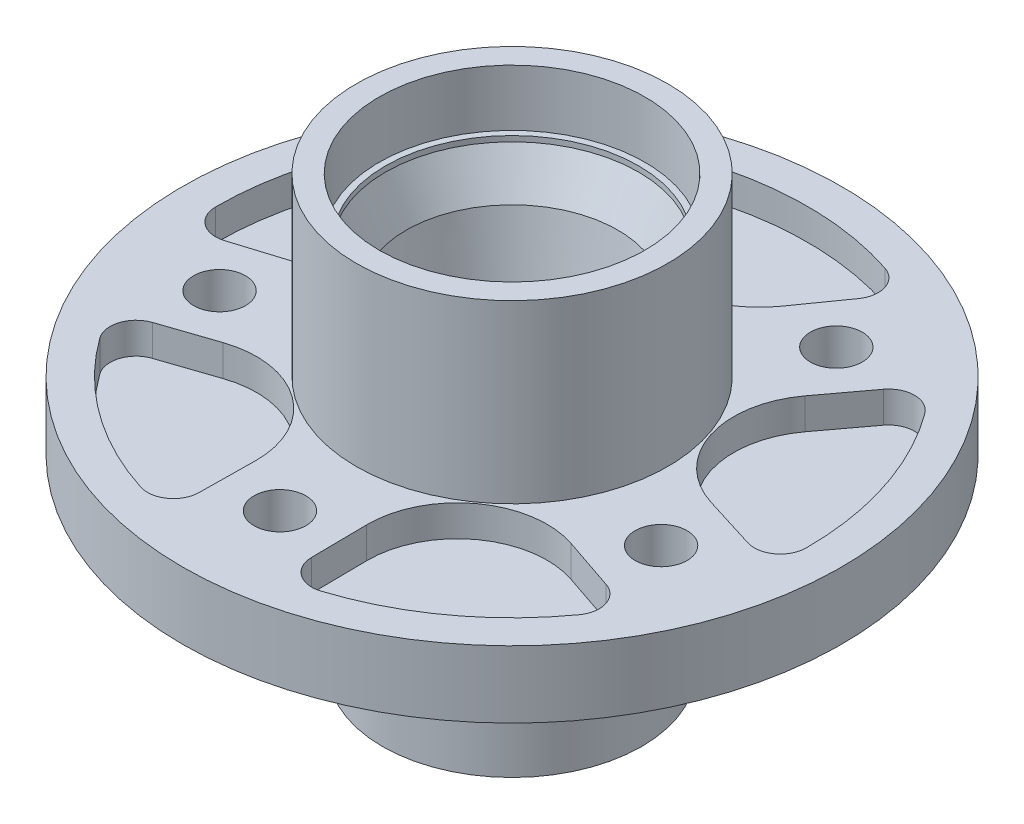
SolidWorks part; units mm, degrees
material "ASTM A36 Steel"
ref_plane "Front Plane" through (0, 0, 0) normal (0, 0, 1) x (1, 0, 0)
ref_plane "Top Plane" through (0, 0, 0) normal (0, 1, 0) x (1, 0, 0)
ref_plane "Right Plane" through (0, 0, 0) normal (1, 0, 0) x (0, 0, -1)
sketch "Sketch1" plane through (0, 0, 0) normal (0, 0, 1) x (1, 0, 0)
  line L0 (0, 66.6082) -> (0, -73.0111) construction
  line L2 (32.512, 43.053) -> (38.1, 43.053)
  line L3 (38.1, 43.053) -> (38.1, 0)
  line L4 (44.3548, 0) -> (-44.3548, 0) construction
  line L5 (38.1, 0) -> (80.645, 0)
  line L6 (80.645, 0) -> (80.645, -16.383)
  line L7 (80.645, -16.383) -> (31.75, -16.383)
  line L8 (31.75, -16.383) -> (31.75, -62.484)
  line L9 (31.75, -62.484) -> (25.4, -62.484)
  line L10 (32.512, 43.053) -> (32.512, 29.21)
  line L11 (32.512, 29.21) -> (30.977, 29.21)
  line L12 (30.977, 29.21) -> (30.977, 27.8812)
  line L13 (30.977, 27.8812) -> (25.9226, 18.1088)
  line L14 (25.9226, 18.1088) -> (26.8586, 18.1088)
  line L15 (26.8586, 18.1088) -> (22.7068, -6.4)
  line L16 (22.7068, -6.4) -> (22.7068, -45.1238)
  line L17 (22.7068, -45.1238) -> (20.5674, -45.1238)
  line L18 (20.5674, -45.1238) -> (25.4, -56.2029)
  line L21 (25.4, -56.2029) -> (25.4, -62.484)
  dimension "D1" = 76.2
  dimension "D2" = 5.588
  dimension "D3" = 16.383
  dimension "D4" = 63.5
  dimension "D5" = 6.35
  dimension "D6" = 46.101
  dimension "D7" = 161.29
  dimension "D8" = 43.053
  dimension "D9" = 13.843
revolve "Revolve1" add sketch "Sketch1" angle 360 mid plane about L0
sketch "Sketch2" plane through (0, 0, 0) normal (0, 1, 0) x (1, 0, 0)
  circle A0 centre (0, 0) radius 56.7989 construction
  circle A1 centre (0, -56.7989) radius 6.35
  dimension "D1" = 12.7
extrude "Cut-Extrude1" cut sketch "Sketch2" against normal through all
ref_axis "Axis1" through (0, 48.3299, 0) along (0, -1, 0)
pattern_circular "CirPattern1" count 5 over 360 about axis through (0, 48.3299, 0) along (0, -1, 0) of "Cut-Extrude1"
sketch "Sketch3" plane through (0, 0, 0) normal (0, 1, 0) x (1, 0, 0)
  line L0 (-25.8161, 58.9292) -> (-17.9181, 47.7801)
  line L1 (25.8161, 58.9292) -> (17.9181, 47.7801)
  line L2 (0, -58.0453) -> (0, 58.0453) construction
  line L3 (-33.3856, 45.9513) -> (-22.2238, 53.8582) construction
  arc A0 (-22.6224, 68.6307) -> (22.6224, 68.6307) centre (0, 0) cw
  arc A1 (-17.9181, 47.7801) -> (17.9181, 47.7801) centre (0, 60.4733) ccw
  arc A2 (-22.6224, 68.6307) -> (-25.8161, 58.9292) centre (-20.6345, 62.5998) ccw
  arc A3 (22.6224, 68.6307) -> (25.8161, 58.9292) centre (20.6345, 62.5998) cw
  circle A4 centre (0, 0) radius 80.645 construction
  dimension "D1" = 8.382
  dimension "D2" = 6.35
extrude "Cut-Extrude2" cut sketch "Sketch3" against normal blind 7.62
pattern_circular "CirPattern2" count 5 over 360 about axis through (0, 48.3299, 0) along (0, -1, 0) of "Cut-Extrude2"
sketch "Sketch4" plane through (0, -16.383, 0) normal (0, -1, 0) x (1, 0, 0)
  circle A1 centre (0, 0) radius 80.645
  circle A2 centre (0, 0) radius 80.645
  circle A4 centre (-33.3856, -45.9513) radius 6.35 construction
  circle A5 centre (33.3856, -45.9513) radius 6.35 construction
  circle A6 centre (54.019, 17.5518) radius 6.35 construction
  circle A7 centre (0, 56.7989) radius 6.35 construction
  circle A8 centre (-54.019, 17.5518) radius 6.35 construction
  circle A9 centre (-33.3856, -45.9513) radius 6.35
  circle A10 centre (33.3856, -45.9513) radius 6.35
  circle A11 centre (54.019, 17.5518) radius 6.35
  circle A12 centre (0, 56.7989) radius 6.35
  circle A13 centre (-54.019, 17.5518) radius 6.35
  dimension "D1" = 0
